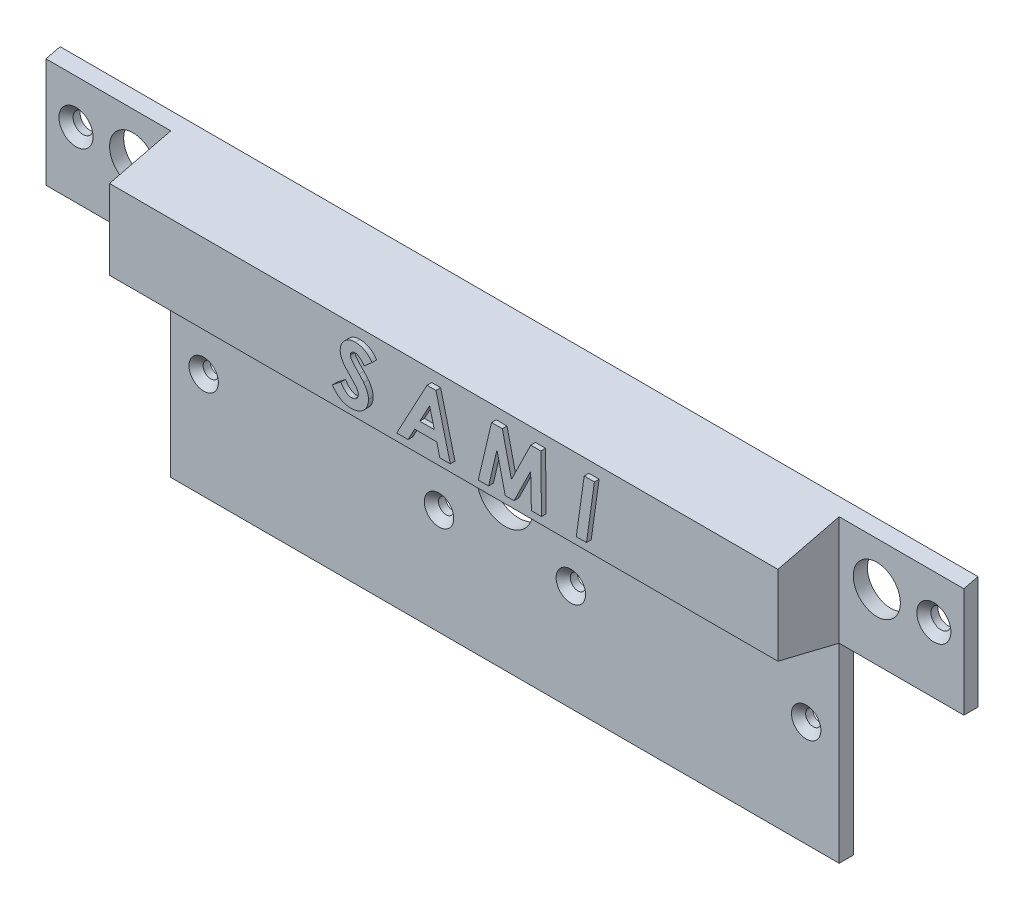
SolidWorks part; units mm, degrees
ref_plane "Alzado" through (0, 0, 0) normal (0, 0, 1) x (1, 0, 0)
ref_plane "Planta" through (0, 0, 0) normal (0, 1, 0) x (1, 0, 0)
ref_plane "Vista lateral" through (0, 0, 0) normal (1, 0, 0) x (0, 0, -1)
sketch "Croquis1" plane through (0, 0, 0) normal (0, 0, 1) x (1, 0, 0)
  line L0 (-97.5, -2) -> (-97.5, -26)
  line L1 (-97.5, -26) -> (-71, -26)
  line L2 (-71, -26) -> (-71, -66.5)
  line L3 (-71, -66.5) -> (71, -66.5)
  line L4 (-97.5, -2) -> (97.5, -2)
  line L5 (0, -66.5) -> (0, 0) construction
  line L6 (71, -26) -> (71, -66.5)
  line L7 (97.5, -26) -> (71, -26)
  line L8 (97.5, -2) -> (97.5, -26)
  circle A0 centre (-91.125, -12.1) radius 2.125
  circle A1 centre (-64, -44) radius 1.625
  circle A2 centre (-14, -44) radius 1.625
  circle A3 centre (14, -44) radius 1.625
  circle A4 centre (64, -44) radius 1.625
  circle A5 centre (91.125, -12.1) radius 2.125
  dimension "D3" = 10.1
  dimension "D4" = 4.25
  dimension "D5" = 6.375
  dimension "D9" = 50
  dimension "D11" = 3.25
  dimension "D1" = 40.5
  dimension "D2" = 24
  dimension "D6" = 33.5
  dimension "D7" = 7
  dimension "D8" = 71
  dimension "D10" = 22.5
extrude "Saliente-Extruir1" add sketch "Croquis1" along normal blind 3
sketch "Croquis2" plane through (0, 0, 3) normal (0, 0, 1) x (1, 0, 0)
  line L0 (97.5, -2) -> (-97.5, -2) construction
  line L1 (-71, -26) -> (71, -26)
  line L2 (-71, -26) -> (-71, -2)
  line L3 (-71, -2) -> (71, -2)
  line L4 (71, -26) -> (71, -2)
  line L5 (71, -66.5) -> (71, -26) construction
extrude "Saliente-Extruir2" add sketch "Croquis2" along normal blind 13
sketch "Croquis4" plane through (-71, 0, 0) normal (-1, 0, 0) x (0, 0, 1)
  line L0 (0, -23) -> (12.2544, -20)
  line L1 (0, -2) -> (0, -26) construction
  line L2 (12.2544, -20) -> (12.2544, -8)
  line L3 (12.2544, -8) -> (0, -5)
  line L4 (0, -5) -> (0, -23)
  line L5 (16, -26) -> (3, -26) construction
  line L6 (16, -2) -> (3, -2) construction
  dimension "D1" = 3
  dimension "D2" = 6
  dimension "D3" = 3
  dimension "D4" = 6
extrude "Cortar-Extruir1" cut sketch "Croquis4" against normal blind 134 from offset 4 offset against normal yes
sketch "Croquis5" plane through (-71, 0, 0) normal (-1, 0, 0) x (0, 0, 1)
  line L0 (3, -26) -> (16, -22.8175)
  line L1 (16, -22.8175) -> (16, -5.9169)
  line L2 (16, -5.9169) -> (0, -2)
  line L3 (0, -2) -> (13.1267, 3.4111)
  line L4 (13.1267, 3.4111) -> (22.4909, -3.1113)
  line L5 (22.4909, -3.1113) -> (22.4909, -28.483)
  line L8 (0, -23) -> (12.2544, -20) construction
  line L9 (12.2544, -8) -> (0, -5) construction
  line L10 (3, -26) -> (22.4909, -28.483)
  line L11 (16, -2) -> (16, -26) construction
  dimension "D1" = 2.483
extrude "Cortar-Extruir2" cut sketch "Croquis5" against normal through all both and the other way through all
sketch "Croquis6" plane through (0, 0, 16) normal (0, 0, 1) x (1, 0, 0)
  line L0 (-71, -20.3175) -> (71, -20.3175) construction
  line L1 (-71, -5.9169) -> (-71, -22.8175) construction
  line L2 (71, -22.8175) -> (71, -5.9169) construction
  line L3 (-71, -22.8175) -> (71, -22.8175) construction
  text T0 "<b><i>     SAMI</i></b>" font "Century Gothic" height 12
  dimension "D1" = 2.5
extrude "Saliente-Extruir3" add sketch "Croquis6" along normal blind 1
chamfer "Chaflán1" distance 1.5 angle 45 6 edges at (-89, -12.1, 3) (89, -12.1, 3) (62.375, -44, 3) (12.375, -44, 3) (-12.375, -44, 3) (-62.375, -44, 3)
sketch "Croquis7" plane through (0, 0, 3) normal (0, 0, 1) x (1, 0, 0)
  line L0 (-71, -26) -> (71, -26) construction
  circle A0 centre (0, -34) radius 6
  dimension "D1" = 12
  dimension "D2" = 8
extrude "Cortar-Extruir3" cut sketch "Croquis7" against normal blind 10
sketch "Croquis11" plane through (0, 0, 3) normal (0, 0, 1) x (1, 0, 0)
  line L0 (0, 0) -> (0, 47.0371) construction
  line L1 (-71, -5.9169) -> (-71, -22.8175) construction
  circle A0 centre (-79, -12.1) radius 5
  circle A1 centre (79, -12.1) radius 5
  dimension "D1" = 10
  dimension "D2" = 8
extrude "Cortar-Extruir7" cut sketch "Croquis11" against normal blind 60
